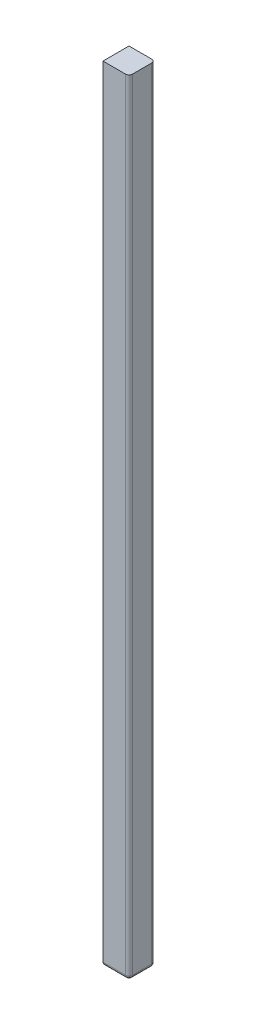
SolidWorks part; units mm, degrees
ref_plane "Front Plane" through (0, 0, 0) normal (0, 0, 1) x (1, 0, 0)
ref_plane "Top Plane" through (0, 0, 0) normal (0, 1, 0) x (1, 0, 0)
ref_plane "Right Plane" through (0, 0, 0) normal (1, 0, 0) x (0, 0, -1)
sketch "Sketch1" plane through (0, 0, 0) normal (0, 1, 0) x (1, 0, 0)
  line L7 (-1.9, -1.9) -> (1.9, -1.9)
  line L8 (-1.9, -1.9) -> (-1.9, 1.9)
  line L9 (-1.9, 1.9) -> (1.9, 1.9)
  line L10 (1.9, -1.9) -> (1.9, 1.9)
  line L11 (-1.9, -1.9) -> (1.9, 1.9) construction
  line L12 (-1.9, 1.9) -> (1.9, -1.9) construction
  dimension "D2" = 3.8
  dimension "D3" = 3.8
extrude "Boss-Extrude1" add sketch "Sketch1" along normal blind 114.3
fillet "Fillet1" radius 0.5 4 edges at (0, 0, 1.9) (0, 0, -1.9) (-1.9, 0, 0) (1.9, 0, 0)
fillet "Fillet2" radius 0.5 4 edges at (1.7536, 0.1464, -1.7536) (1.7536, 0.1464, 1.7536) (1.9, 57.4, -1.9) (1.9, 57.4, 1.9)
